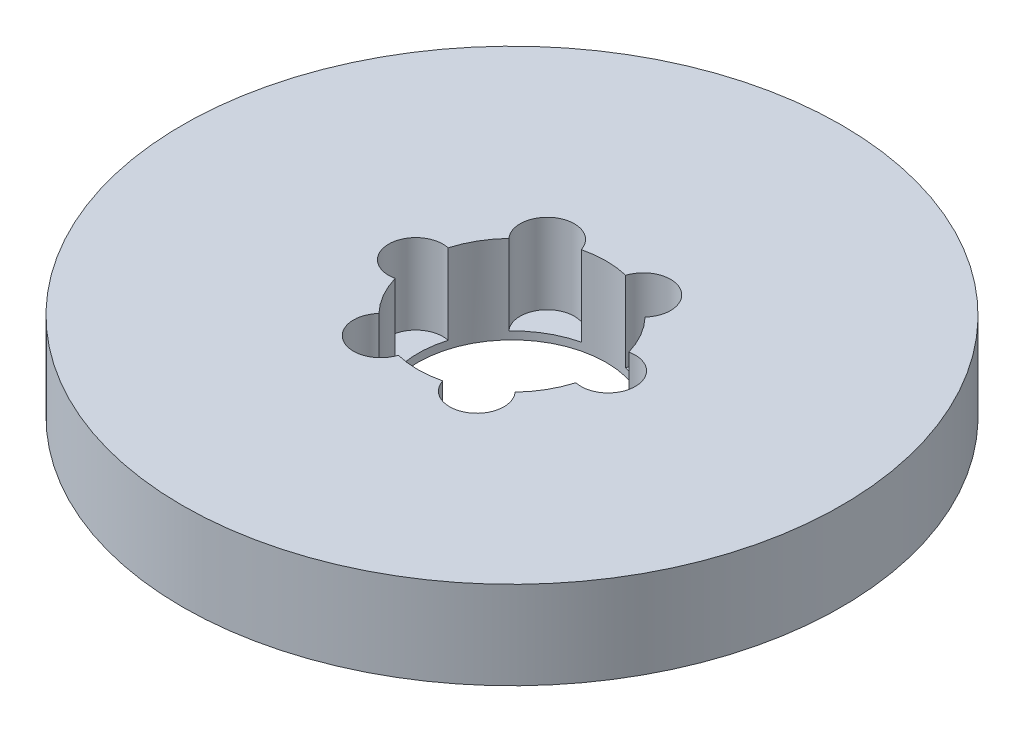
SolidWorks part; units mm, degrees
ref_plane "Front Plane" through (0, 0, 0) normal (0, 0, 1) x (1, 0, 0)
ref_plane "Top Plane" through (0, 0, 0) normal (0, 1, 0) x (1, 0, 0)
ref_plane "Right Plane" through (0, 0, 0) normal (1, 0, 0) x (0, 0, -1)
sketch "Sketch1" plane through (0, 0, 0) normal (0, 1, 0) x (1, 0, 0)
  circle A0 centre (0, 0) radius 52.5
  dimension "FLANGE_OD" = 105
extrude "Boss-Extrude1" add sketch "Sketch1" along normal blind 14
sketch "Sketch2" plane through (0, 0, 0) normal (0, 1, 0) x (1, 0, 0)
  circle A0 centre (0, 0) radius 15
  dimension "BORE_D" = 30
extrude "Cut-Extrude1" cut sketch "Sketch2" along normal through all
sketch "Sketch3" plane through (0, 14, 0) normal (0, 1, 0) x (1, 0, 0)
  circle A0 centre (0, 0) radius 15.3241 construction
  circle A1 centre (-15.3241, 0) radius 4.3229
  dimension "BOLT_D" = 8.6457
  dimension "BOLT_PCD" = 30.6481
extrude "Cut-Extrude2" cut sketch "Sketch3" against normal blind 12.7598
pattern_circular "CirPattern1" count 6 over 360 about axis through (0, 0, 0) along (0, 1, 0) of "Cut-Extrude2"
